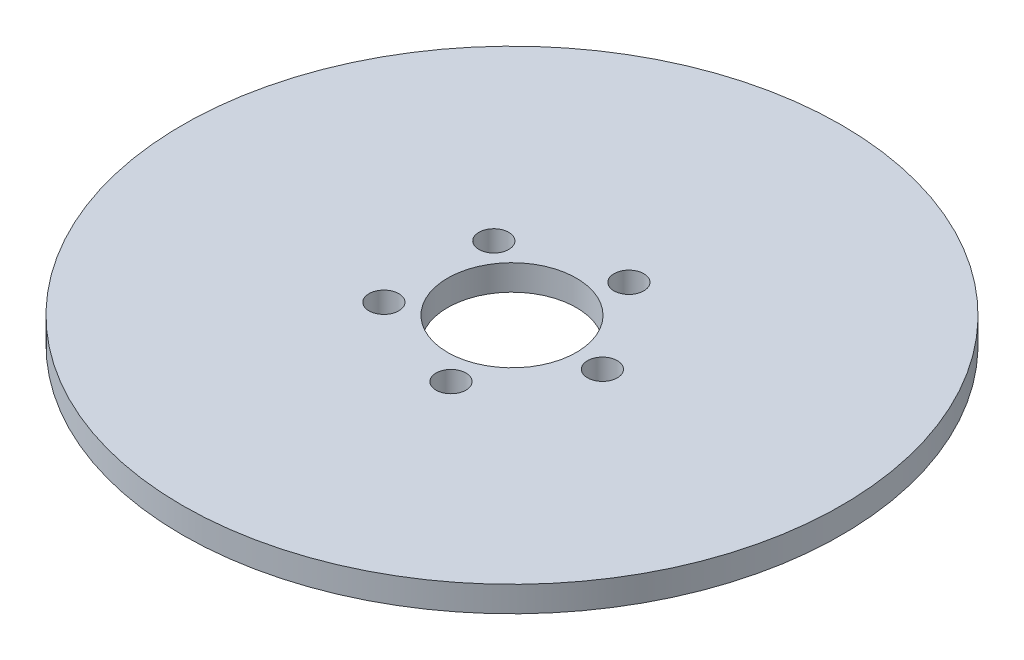
SolidWorks part; units mm, degrees
material "6061 Alloy"
ref_plane "Front Plane" through (0, 0, 0) normal (0, 0, 1) x (1, 0, 0)
ref_plane "Top Plane" through (0, 0, 0) normal (0, 1, 0) x (1, 0, 0)
ref_plane "Right Plane" through (0, 0, 0) normal (1, 0, 0) x (0, 0, -1)
sketch "Sketch1" plane through (0, 1054.464, 0) normal (0, 1, 0) x (-1, 0, 0)
  circle A0 centre (1.2041, -633.1149) radius 40.95
  circle A2 centre (1.2041, -633.1149) radius 40.95 construction
  circle A3 centre (10.3365, -639.9883) radius 1.8542 construction
  circle A4 centre (-2.5108, -643.9243) radius 1.8542 construction
  circle A5 centre (-10.2243, -632.9221) radius 1.8542 construction
  circle A6 centre (10.5632, -626.5534) radius 1.8542 construction
  circle A7 centre (-2.1441, -622.1863) radius 1.8542 construction
  circle A8 centre (1.2041, -633.1149) radius 8.001
  circle A9 centre (10.3365, -639.9883) radius 1.8542
  circle A10 centre (-2.5108, -643.9243) radius 1.8542
  circle A11 centre (-10.2243, -632.9221) radius 1.8542
  circle A12 centre (10.5632, -626.5534) radius 1.8542
  circle A13 centre (-2.1441, -622.1863) radius 1.8542
  dimension "D1" = 16.002
extrude "Boss-Extrude1" add sketch "Sketch1" against normal blind 3.175
